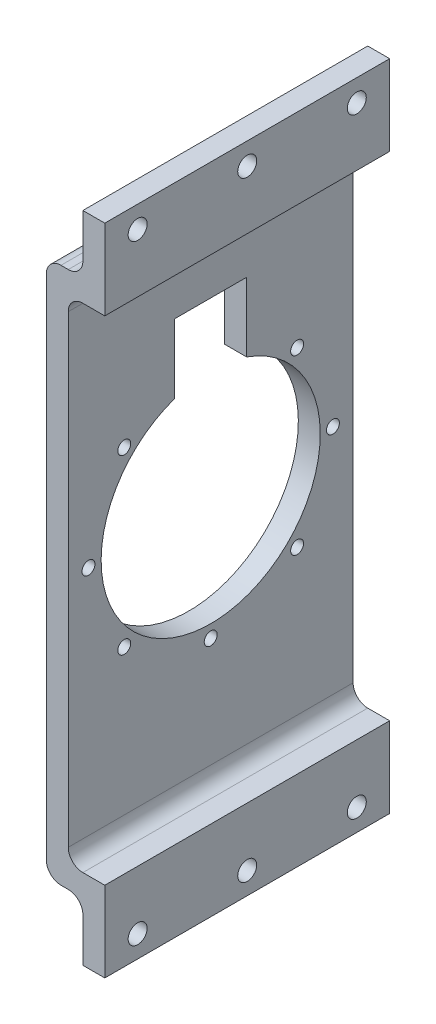
SolidWorks part; units mm, degrees
other "Markup1"
sketch "Sketch9" plane through (-7.62, -27.94, -49.53) normal (-1, 0, 0) x (0, 0, 1)
sketch "Sketch12" plane through (-7.62, -27.94, -49.53) normal (-1, 0, 0) x (0, 0, 1)
sketch "Sketch13" plane through (-7.62, -27.94, -49.53) normal (-1, 0, 0) x (0, 0, 1)
sketch "Sketch15" plane through (-7.62, -27.94, -49.53) normal (-1, 0, 0) x (0, 0, 1)
sketch "Sketch16" plane through (-7.62, -27.94, -49.53) normal (-1, 0, 0) x (0, 0, 1)
material "ABS"
ref_plane "Front Plane" through (0, 0, 0) normal (0, 0, 1) x (1, 0, 0)
ref_plane "Top Plane" through (0, 0, 0) normal (0, 1, 0) x (1, 0, 0)
ref_plane "Right Plane" through (0, 0, 0) normal (1, 0, 0) x (0, 0, -1)
sketch "Sketch1" plane through (0, 0, 0) normal (0, 0, 1) x (1, 0, 0)
  line L0 (0, 0) -> (0, 171.45)
  line L1 (0, 0) -> (12.7, 0)
  line L2 (-7.62, -7.62) -> (-7.62, 171.45)
  line L3 (-7.62, -7.62) -> (5.08, -7.62)
  line L5 (12.7, 0) -> (12.7, -7.62)
  line L8 (0, 171.45) -> (12.7, 171.45)
  line L9 (-7.62, 171.45) -> (-7.62, 179.07)
  line L10 (-7.62, 179.07) -> (5.08, 179.07)
  line L11 (12.7, 171.45) -> (12.7, 179.07)
  line L12 (12.7, -7.62) -> (12.7, -27.94)
  line L13 (12.7, -27.94) -> (5.08, -27.94)
  line L14 (5.08, -27.94) -> (5.08, -7.62)
  line L15 (12.7, 179.07) -> (12.7, 199.39)
  line L16 (-7.62, -7.62) -> (12.7, -7.62) construction
  line L17 (12.7, 199.39) -> (5.08, 199.39)
  line L18 (5.08, 199.39) -> (5.08, 179.07)
  dimension "D3" = 20.32
  dimension "D4" = 171.45
  dimension "D2" = 20.32
  dimension "D1" = 7.62
extrude "Boss-Extrude1" add sketch "Sketch1" along normal mid plane 99.06
ref_plane "Actuator Plane" through (0, 85.725, 0) normal (0, 1, 0) x (1, 0, 0)
fillet "Fillet1" radius 5.08 6 edges at (0, 0, 0) (5.08, -7.62, 0) (0, 171.45, 0) (5.08, 179.07, 0) (-7.62, 179.07, 0) (-7.62, -7.62, 0)
sketch "Sketch7" plane through (0, 0, 0) normal (1, 0, 0) x (0, 0, -1)
  line L0 (4.191, 85.725) -> (-4.191, 85.725) construction
  line L3 (-39.2649, 101.989) -> (0, 85.725) construction
  line L4 (0, 85.725) -> (-42.5, 85.725) construction
  circle A0 centre (0, 85.725) radius 42.5 construction
  circle A1 centre (-42.5, 85.725) radius 2.25
  circle A2 centre (-30.052, 115.777) radius 2.25
  circle A3 centre (0, 128.225) radius 2.25
  circle A4 centre (30.052, 115.777) radius 2.25
  circle A5 centre (42.5, 85.725) radius 2.25
  circle A6 centre (30.052, 55.673) radius 2.25
  circle A7 centre (0, 43.225) radius 2.25
  circle A8 centre (-30.052, 55.673) radius 2.25
  circle A9 centre (-39.2649, 101.989) radius 1.75 construction
  circle A10 centre (-16.264, 124.9899) radius 1.75 construction
  circle A11 centre (16.264, 124.9899) radius 1.75 construction
  circle A12 centre (39.2649, 101.989) radius 1.75 construction
  circle A13 centre (39.2649, 69.461) radius 1.75 construction
  circle A14 centre (16.264, 46.4601) radius 1.75 construction
  circle A15 centre (-16.264, 46.4601) radius 1.75 construction
  circle A16 centre (-39.2649, 69.461) radius 1.75 construction
  circle A17 centre (0, 85.725) radius 38.1
  point P28 (0, 85.725)
  point P45 (0, 85.725)
  dimension "D1" = 4.5
  dimension "D2" = 85
  dimension "D5" = 3.5
  dimension "D7" = 76.2
  dimension "D4" = 22.5
  dimension "D3" = 8
  dimension "D6" = 8
extrude "Cut-Extrude1" cut sketch "Sketch7" against normal up to surface (7.62 mm away) up to face at (-7.62, 85.725, 0)
sketch "Sketch8" plane through (5.08, 0, 0) normal (-1, 0, 0) x (0, 0, 1)
  line L0 (-38.1, 191.77) -> (0, 191.77) construction
  line L1 (0, 191.77) -> (38.1, 191.77) construction
  line L2 (0, -55) -> (0, 55) construction
  line L4 (-49.53, 199.39) -> (-49.53, 184.15) construction
  circle A0 centre (-38.1, 191.77) radius 3.302
  circle A1 centre (0, 191.77) radius 3.302
  circle A3 centre (38.1, 191.77) radius 3.302
  point P17 (-49.53, 191.77)
  dimension "D4" = 6.604
  dimension "D2" = 76.2
extrude "Cut-Extrude2" cut sketch "Sketch8" against normal up to surface (7.62 mm away) up to face at (12.7, 185.42, 0)
mirror "Mirror1" about plane through (0, 85.725, 0) normal (0, 1, 0) of "Cut-Extrude2"
sketch "Sketch14" plane through (-7.62, 0, 0) normal (-1, 0, 0) x (0, 0, 1)
  line L0 (12.5, 121.7161) -> (12.5, 145.725)
  line L1 (12.5, 145.725) -> (-12.5, 145.725)
  line L2 (-12.5, 145.725) -> (-12.5, 121.7161)
  circle A0 centre (0, 85.725) radius 38.1 construction
  arc A1 (12.5, 121.7161) -> (-12.5, 121.7161) centre (0, 85.725) ccw
  point P10 (0, 145.725)
  dimension "D1" = 25
  dimension "D2" = 60
extrude "Cut-Extrude3" cut sketch "Sketch14" against normal up to surface (7.62 mm away) up to face at (0, 85.725, 40.25)
equation "\"VerticalHeight\"= 6.75"
equation "\"D4@Sketch1\"=\"VerticalHeight\""
